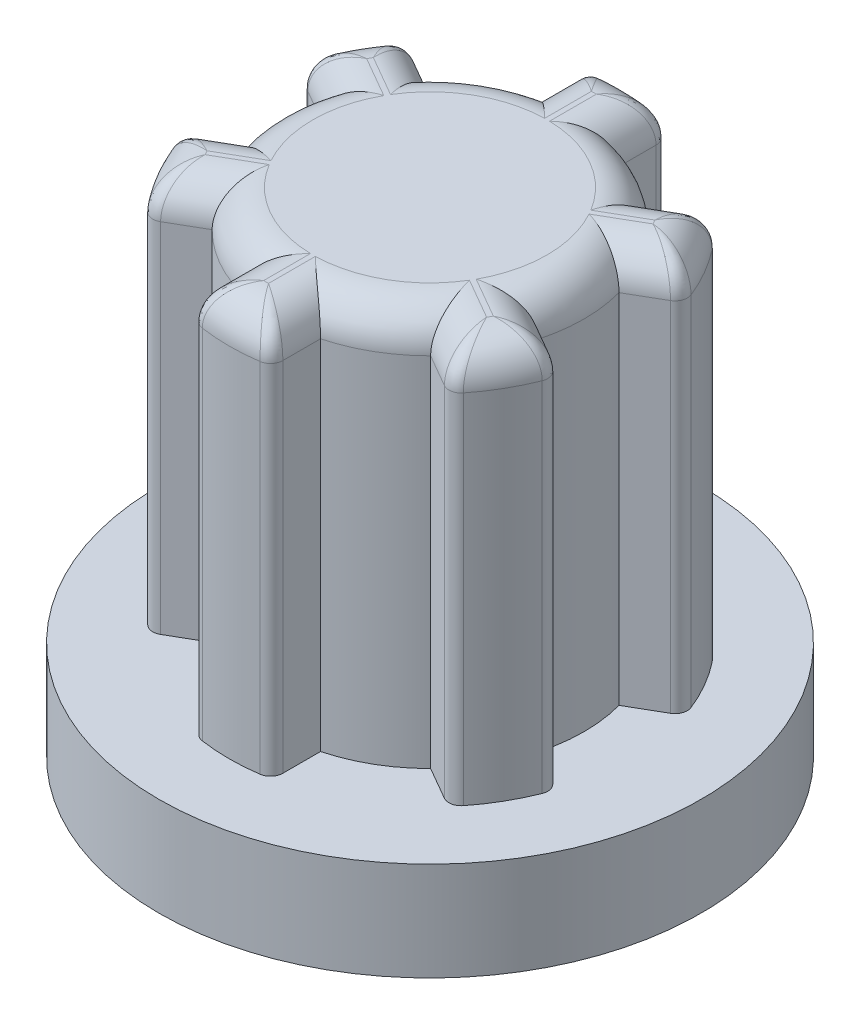
SolidWorks part; units mm, degrees
ref_plane "Спереди" through (0, 0, 0) normal (0, 0, 1) x (1, 0, 0)
ref_plane "Сверху" through (0, 0, 0) normal (0, 1, 0) x (1, 0, 0)
ref_plane "Справа" through (0, 0, 0) normal (1, 0, 0) x (0, 0, -1)
sketch "Эскиз1" plane through (0, 0, 0) normal (0, 0, 1) x (1, 0, 0)
  line L0 (0, 0) -> (0, -7.3623) construction
  line L1 (0, 0) -> (-8.25, 0) construction
  line L2 (-9.75, 0) -> (-11, 0)
  line L3 (-11, 0) -> (-11, 4)
  line L4 (-11, 4) -> (-8.15, 4)
  line L5 (-8.15, 4) -> (-8.15, 20)
  line L6 (-8.15, 20) -> (0, 20)
  line L7 (0, 20) -> (0, 17)
  line L8 (-3.75, 3) -> (-8.25, 3)
  line L9 (-8.25, 3) -> (-8.25, 2)
  line L10 (-3.75, 3) -> (-3.75, 17)
  line L11 (-3.75, 17) -> (0, 17)
  line L12 (-8.25, 2) -> (-9.75, 2)
  line L13 (-9.75, 2) -> (-9.75, 0)
  dimension "D1" = 22
  dimension "D2" = 16.3
  dimension "D3" = 4
  dimension "D4" = 20
  dimension "D5" = 16.5
  dimension "D6" = 7.5
  dimension "D7" = 19.5
  dimension "D8" = 2
  dimension "D9" = 3
  dimension "D10" = 3
revolve "Повернуть1" add sketch "Эскиз1" angle 360 about L0
sketch "Эскиз2" plane through (0, 20, 0) normal (0, 1, 0) x (1, 0, 0)
  line L0 (0, 0) -> (0, 8.15) construction
  line L1 (-1.6, 7.9914) -> (-1.6, 6.0417)
  line L2 (1.6, 7.9914) -> (1.6, 6.0417)
  line L3 (6.1208, 5.3813) -> (4.4323, 4.4065)
  line L4 (7.7208, 2.6101) -> (6.0323, 1.6352)
  line L5 (7.7208, -2.6101) -> (6.0323, -1.6352)
  line L6 (6.1208, -5.3813) -> (4.4323, -4.4065)
  line L7 (1.6, -7.9914) -> (1.6, -6.0417)
  line L8 (-1.6, -7.9914) -> (-1.6, -6.0417)
  line L9 (-6.1208, -5.3813) -> (-4.4323, -4.4065)
  line L10 (-7.7208, -2.6101) -> (-6.0323, -1.6352)
  line L11 (-7.7208, 2.6101) -> (-6.0323, 1.6352)
  line L12 (-6.1208, 5.3813) -> (-4.4323, 4.4065)
  circle A0 centre (0, 0) radius 8.15
  circle A1 centre (0, 0) radius 6.25
  point P32 (0, 0)
  circle M5 centre (0, 0) radius 8.15
  dimension "D1" = 12.5
  dimension "D2" = 16.3
  dimension "D3" = 3.2
  dimension "D4" = 6
extrude "Вырез-Вытянуть1" cut sketch "Эскиз2" against normal blind 16 contours A1 L1 L12 M5 | A1 L3 L2 M5 | A1 L5 L4 M5 | A1 L7 L6 M5 | A1 L9 L8 M5 | A1 L11 L10 M5 region at (-3.5817, 20, -6.2036) region at (3.5817, 20, -6.2036) region at (-7.1634, 20, 0) region at (7.1634, 20, 0) region at (-3.5817, 20, 6.2036) region at (3.5817, 20, 6.2036)
fillet "Скругление1" radius 1.5 24 edges at (-6.8765, 20, -2.1226) (-5.2765, 20, -4.8939) (-6.25, 20, 0) (-7.0581, 20, -4.075) (-3.125, 20, -5.4127) (-1.6, 20, -7.0166) (0, 20, -8.15) (1.6, 20, -7.0166) (3.125, 20, -5.4127) (5.2765, 20, -4.8939) (7.0581, 20, -4.075) (6.8765, 20, -2.1226) (6.25, 20, 0) (6.8765, 20, 2.1226) (7.0581, 20, 4.075) (5.2765, 20, 4.8939) (3.125, 20, 5.4127) (1.6, 20, 7.0166) (0, 20, 8.15) (-1.6, 20, 7.0166) (-3.125, 20, 5.4127) (-5.2765, 20, 4.8939) (-7.0581, 20, 4.075) (-6.8765, 20, 2.1226)
fillet "Скругление2" radius 0.5 24 edges at (6.0736, 19.2764, 5.104) (7.457, 19.2764, 2.7078) (7.457, 19.2764, -2.7078) (6.0736, 19.2764, -5.104) (1.3834, 19.2764, -7.8119) (-1.3834, 19.2764, -7.8119) (-6.0736, 19.2764, -5.104) (-7.457, 19.2764, -2.7078) (-7.457, 19.2764, 2.7078) (-6.0736, 19.2764, 5.104) (-1.3834, 19.2764, 7.8119) (1.3834, 19.2764, 7.8119) (6.1208, 11.25, 5.3813) (7.7208, 11.25, 2.6101) (7.7208, 11.25, -2.6101) (6.1208, 11.25, -5.3813) (1.6, 11.25, -7.9914) (-1.6, 11.25, -7.9914) (-6.1208, 11.25, -5.3813) (-7.7208, 11.25, -2.6101) (-7.7208, 11.25, 2.6101) (-6.1208, 11.25, 5.3813) (-1.6, 11.25, 7.9914) (1.6, 11.25, 7.9914)
